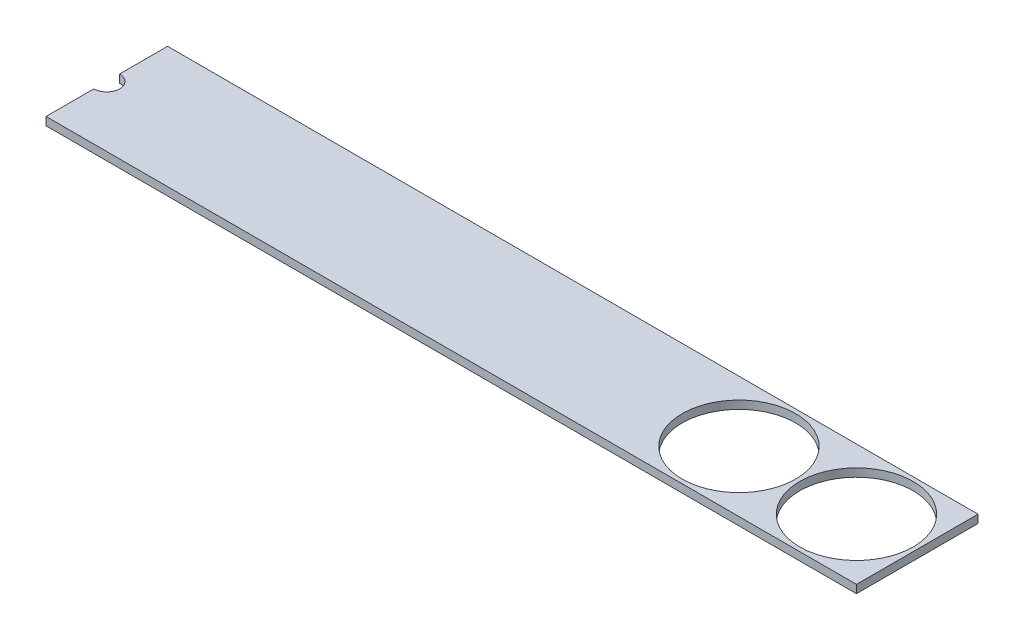
SolidWorks part; units mm, degrees
ref_plane "Front Plane" through (0, 0, 0) normal (0, 0, 1) x (1, 0, 0)
ref_plane "Top Plane" through (0, 0, 0) normal (0, 1, 0) x (1, 0, 0)
ref_plane "Right Plane" through (0, 0, 0) normal (1, 0, 0) x (0, 0, -1)
sketch "Sketch1" plane through (0, 0, 0) normal (0, 1, 0) x (1, 0, 0)
  line L1 (-100, 15) -> (100, 15)
  line L2 (-100, 15) -> (-100, -15)
  line L3 (-100, -15) -> (100, -15)
  line L4 (100, 15) -> (100, -15)
  line L5 (-100, 15) -> (100, -15) construction
  line L6 (-100, -15) -> (100, 15) construction
  circle A0 centre (85, 0) radius 14
  circle A1 centre (56, 0) radius 14
  circle A2 centre (-100, 0) radius 3.185
  arc A3 (-100, -3.185) -> (-100, 3.185) centre (-100, 0) ccw
  point P0 (0, 0)
  dimension "D3" = 28
  dimension "D5" = 15
  dimension "D7" = 6.37
  dimension "D1" = 200
  dimension "D2" = 30
  dimension "D4" = 15
  dimension "D6" = 29
  dimension "D8" = 0
extrude "Boss-Extrude3" add sketch "Sketch1" along normal blind 2 contours L2 L1 L4 L3 | A1 | A0
extrude "Cut-Extrude1" cut sketch "Sketch1<7>" along normal blind 10 contours A2
sketch "Sketch1<7>" plane through (0, 0, 0) normal (0, 1, 0) x (1, 0, 0) same geometry as "Sketch1"
